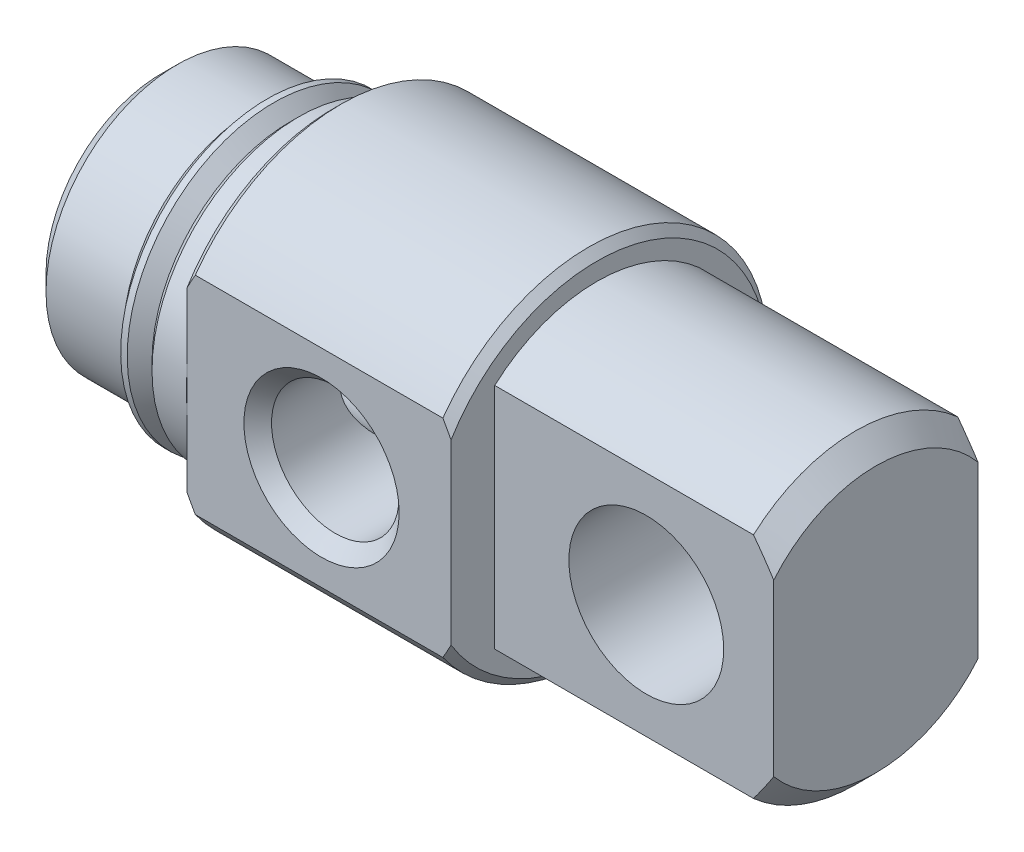
SolidWorks part; units mm, degrees
material "Cast Alloy Steel"
ref_plane "Front Plane" through (0, 0, 0) normal (0, 0, 1) x (1, 0, 0)
ref_plane "Top Plane" through (0, 0, 0) normal (0, 1, 0) x (1, 0, 0)
ref_plane "Right Plane" through (0, 0, 0) normal (1, 0, 0) x (0, 0, -1)
ref_plane "Plane1" through (22.225, 0, 0) normal (1, 0, 0) x (0, 0, -1)
sketch "Sketch1" plane through (0, 0, 0) normal (0, 0, 1) x (1, 0, 0)
  line L0 (0, 0) -> (0, 3.5751)
  line L1 (0, 3.5751) -> (0.508, 4.0831)
  line L2 (0.508, 4.0831) -> (2.9083, 4.0831)
  line L3 (2.9083, 4.0831) -> (3.4671, 3.5242)
  line L4 (3.4671, 3.5242) -> (4.0259, 3.5242)
  line L5 (4.0259, 3.5242) -> (4.0259, 4.3053)
  line L6 (4.0259, 4.3053) -> (4.2799, 4.5593)
  line L7 (4.2799, 4.5593) -> (5.3467, 4.5593)
  line L8 (5.3467, 4.5593) -> (5.3467, 5.3086)
  line L9 (5.3467, 5.3086) -> (5.6007, 5.5626)
  line L10 (5.6007, 5.5626) -> (13.2969, 5.5626)
  line L11 (13.2969, 5.5626) -> (13.5509, 5.3086)
  line L12 (13.5509, 5.3086) -> (13.5509, 0)
  line L13 (13.5509, 0) -> (0, 0)
  line L14 (13.5509, 0) -> (0, 0) construction
revolve "Revolve1" add sketch "Sketch1" angle 360 about L14 reverse direction yes
sketch "Sketch2" plane through (0, 0, 0) normal (0, 0, 1) x (1, 0, 0)
  line L0 (13.5509, 0) -> (13.5509, 4.7625)
  line L1 (13.5509, 4.7625) -> (21.5951, 4.7625)
  line L2 (21.5951, 4.7625) -> (22.225, 4.1326)
  line L3 (22.225, 4.1326) -> (22.225, 0)
  line L4 (22.225, 0) -> (13.5509, 0)
  line L5 (22.225, 0) -> (13.5509, 0) construction
revolve "Revolve2" add sketch "Sketch2" angle 360 about L5 reverse direction yes
cosmetic thread "Cosmetic Thread1" parameters "D1"=8.6741, "D2"=8.2652
sketch "Sketch3" plane through (22.225, 0, 0) normal (1, 0, 0) x (0, 0, -1)
  line L0 (-11.1252, -22.2504) -> (11.1252, -22.2504)
  line L1 (11.1252, -22.2504) -> (11.1252, 22.2504)
  line L2 (11.1252, 22.2504) -> (-11.1252, 22.2504)
  line L3 (-11.1252, 22.2504) -> (-11.1252, -22.2504)
  line L4 (-3.175, -11.1252) -> (3.175, -11.1252)
  line L5 (3.175, -11.1252) -> (3.175, 11.1252)
  line L6 (3.175, 11.1252) -> (-3.175, 11.1252)
  line L7 (-3.175, 11.1252) -> (-3.175, -11.1252)
extrude "Cut-Extrude1" cut sketch "Sketch3" against normal blind 8.6741
ref_plane "Plane2" through (13.5509, 0, 0) normal (1, 0, 0) x (0, 0, -1)
sketch "Sketch4" plane through (13.5509, 0, 0) normal (1, 0, 0) x (0, 0, -1)
  line L0 (-10.0965, 5.5626) -> (-10.0965, -5.5626)
  line L1 (-10.0965, -5.5626) -> (-4.5339, -5.5626)
  line L2 (-4.5339, -5.5626) -> (-4.5339, 5.5626)
  line L3 (-4.5339, 5.5626) -> (-10.0965, 5.5626)
extrude "Cut-Extrude2" cut sketch "Sketch4" against normal blind 8.2042
hole_wizard "Hole1" positions "Sketch6" profile "Sketch5" legacy
sketch "Sketch6" plane through (0, 0, 0) normal (-1, 0, 0) x (0, 0, 1)
  point P0 (0, 0)
sketch "Sketch5" plane through (0, 0, 0) normal (0, 1, 0) x (0, 0, 1)
  line L0 (0, 0) -> (0, 14.6962)
  line L1 (0, 14.6962) -> (1.9837, 13.5509)
  line L2 (1.9837, 13.5509) -> (1.9837, 0)
  line L4 (1.9837, 0) -> (0, 0)
  line L6 (0, 14.6962) -> (-1.9837, 13.5509) construction
  line L7 (0, -4.2442) -> (0, 117.3081) construction
  dimension "Diameter" = 3.9675
  dimension "Depth" = 13.5509
  dimension "Drill Angle" = 120
hole_wizard "Hole2" positions "Sketch8" profile "Sketch7" legacy
sketch "Sketch8" plane through (0, 0, 4.5339) normal (0, 0, 1) x (1, 0, 0)
  point P0 (9.525, 0)
sketch "Sketch7" plane through (9.525, 0, 4.5339) normal (1, 0, 0) x (0, -1, 0)
  line L0 (0, 0) -> (0, 4.5339)
  line L1 (0, 4.5339) -> (1.9837, 4.5339)
  line L2 (1.9837, 4.5339) -> (1.9837, 0.4293)
  line L3 (1.9837, 0.4293) -> (2.413, 0)
  line L4 (2.413, 0) -> (0, 0)
  line L5 (0, -6.4453) -> (0, 115.525) construction
  line L6 (-1.9837, 0.4293) -> (-2.413, 0) construction
  dimension "Diameter" = 3.9675
  dimension "Depth" = 4.5339
  dimension "C-Sink Angle" = 90
  dimension "C-Sink Diameter" = 4.826
cosmetic thread "Cosmetic Thread2" parameters "D1"=2.5502, "D2"=4.826
ref_plane "Plane3" through (0, 0, 0) normal (0, 0.9998, 0.0175) x (1, 0, 0)
ref_plane "Plane4" through (9.525, 0, 0) normal (1, 0, 0) x (0, 0, -1)
ref_plane "Plane5" through (3.4671, 0, 0) normal (1, 0, 0) x (0, 0, -1)
sketch "Sketch9" plane through (0, 0, 0) normal (0, 0, 1) x (1, 0, 0)
  line L0 (3.3065, 4.4751) -> (3.9121, 3.8695)
  line L1 (3.9121, 3.6899) -> (3.7465, 3.5242)
  line L2 (3.7465, 3.5242) -> (3.4671, 3.5242)
  line L3 (3.4671, 3.5242) -> (3.4671, 3.2703)
  line L4 (3.4671, 3.2703) -> (4.0259, 3.2703)
  line L5 (4.0259, 3.2703) -> (4.0259, 4.0431)
  line L6 (4.0259, 4.0431) -> (3.5097, 4.5593)
  line L7 (3.5097, 4.5593) -> (3.3065, 4.5593)
  line L8 (3.3065, 4.5593) -> (3.3065, 4.4751)
  line L9 (4.0259, 0) -> (3.4671, 0) construction
  arc A0 (3.9121, 3.8695) -> (3.9121, 3.6899) centre (3.8223, 3.7797) cw
revolve "Revolve3" add sketch "Sketch9" angle 360 about L9 reverse direction yes
ref_plane "Plane6" through (22.352, 0, 0) normal (1, 0, 0) x (0, 0, -1)
sketch "Sketch10" plane through (0, 0, 0) normal (0, 0, 1) x (1, 0, 0)
  circle A0 centre (18.2626, 0) radius 2.4066
extrude "Cut-Extrude3" cut sketch "Sketch10" along normal blind 4.7625 and the other way blind 4.7625
ref_plane "Plane7" through (13.5509, 0, 0) normal (1, 0, 0) x (0, 0, -1)
ref_plane "Plane8" through (22.225, 0, 0) normal (1, 0, 0) x (0, 0, -1)
ref_plane "Plane9" through (18.2626, 0, 0) normal (1, 0, 0) x (0, 0, -1)
ref_plane "Plane10" through (22.225, 0, 0) normal (1, 0, 0) x (0, 0, -1)
ref_plane "Plane11" through (0, 0, 0) normal (0, 0, 1) x (1, 0, 0)
ref_plane "Plane12" through (13.5509, 0, 0) normal (1, 0, 0) x (0, 0, -1)
ref_plane "Plane13" through (0, 0, 0) normal (0, 1, 0) x (1, 0, 0)
ref_plane "Plane14" through (0, 0, 0) normal (0, 1, 0) x (1, 0, 0)
ref_plane "Plane15" through (13.5509, 0, 0) normal (1, 0, 0) x (0, 0, -1)
ref_plane "1 XY" through (13.5509, 0, 0) normal (1, 0, 0) x (0, 0, -1)
ref_plane "1 XZ" through (0, 0, 0) normal (0, -1, 0) x (-1, 0, 0)
ref_plane "1 YZ" through (0, 0, 0) normal (0, 0, -1) x (-1, 0, 0)
ref_axis "1 X" through (13.5509, 0, 80.9) along (0, 0, -1)
ref_axis "1 Y" through (13.5509, -50, 0) along (0, 1, 0)
ref_axis "1 Z" through (80.9, 0, 0) along (-1, 0, 0)
sketch3d "1"
  point P0 (13.5509, 0, 0)
ref_plane "lovra1 XY" through (22.225, 0, 0) normal (1, 0, 0) x (0, 0, -1)
ref_plane "lovra1 XZ" through (0, 0, 0) normal (0, -1, 0) x (-1, 0, 0)
ref_plane "lovra1 YZ" through (0, 0, 0) normal (0, 0, -1) x (-1, 0, 0)
ref_axis "lovra1 X" through (22.225, 0, 80.9) along (0, 0, -1)
ref_axis "lovra1 Y" through (22.225, -50, 0) along (0, 1, 0)
ref_axis "lovra1 Z" through (80.9, 0, 0) along (-1, 0, 0)
sketch3d "lovra1"
  point P0 (22.225, 0, 0)
ref_plane "lovra2 XY" through (22.225, 0, 0) normal (1, 0, 0) x (0, 0, -1)
ref_plane "lovra2 XZ" through (0, 0, 0) normal (0, -1, 0) x (-1, 0, 0)
ref_plane "lovra2 YZ" through (0, 0, 0) normal (0, 0, -1) x (-1, 0, 0)
ref_axis "lovra2 X" through (22.225, 0, 80.9) along (0, 0, -1)
ref_axis "lovra2 Y" through (22.225, -50, 0) along (0, 1, 0)
ref_axis "lovra2 Z" through (80.9, 0, 0) along (-1, 0, 0)
sketch3d "lovra2"
  point P0 (22.225, 0, 0)
ref_plane "lovra21 XY" through (0, 0, 0) normal (1, 0, 0) x (0, 0, -1)
ref_plane "lovra21 XZ" through (0, 0, 0) normal (0, -1, 0) x (-1, 0, 0)
ref_plane "lovra21 YZ" through (0, 0, 5.2705) normal (0, 0, -1) x (-1, 0, 0)
ref_axis "lovra21 X" through (0, 0, 80.9) along (0, 0, -1)
ref_axis "lovra21 Y" through (0, -50, 5.2705) along (0, 1, 0)
ref_axis "lovra21 Z" through (80.9, 0, 5.2705) along (-1, 0, 0)
sketch3d "lovra21"
  point P0 (0, 0, 5.2705)
ref_plane "lovra22 XY" through (0, 0, 0) normal (1, 0, 0) x (0, 0, -1)
ref_plane "lovra22 XZ" through (0, 0, 0) normal (0, -1, 0) x (-1, 0, 0)
ref_plane "lovra22 YZ" through (0, 0, -5.2705) normal (0, 0, -1) x (-1, 0, 0)
ref_axis "lovra22 X" through (0, 0, 80.9) along (0, 0, -1)
ref_axis "lovra22 Y" through (0, -50, -5.2705) along (0, 1, 0)
ref_axis "lovra22 Z" through (80.9, 0, -5.2705) along (-1, 0, 0)
sketch3d "lovra22"
  point P0 (0, 0, -5.2705)
ref_plane "lovra3 XY" through (22.225, 0, 0) normal (1, 0, 0) x (0, 0, -1)
ref_plane "lovra3 XZ" through (0, 0, 0) normal (0, -1, 0) x (-1, 0, 0)
ref_plane "lovra3 YZ" through (0, 0, 0) normal (0, 0, -1) x (-1, 0, 0)
ref_axis "lovra3 X" through (22.225, 0, 80.9) along (0, 0, -1)
ref_axis "lovra3 Y" through (22.225, -50, 0) along (0, 1, 0)
ref_axis "lovra3 Z" through (80.9, 0, 0) along (-1, 0, 0)
sketch3d "lovra3"
  point P0 (22.225, 0, 0)
ref_plane "olen XY" through (18.2626, 0, 0) normal (1, 0, 0) x (0, 0, -1)
ref_plane "olen XZ" through (0, 0, 0) normal (0, -1, 0) x (-1, 0, 0)
ref_plane "olen YZ" through (0, 0, 0) normal (0, 0, -1) x (-1, 0, 0)
ref_axis "olen X" through (18.2626, 0, 80.9) along (0, 0, -1)
ref_axis "olen Y" through (18.2626, -50, 0) along (0, 1, 0)
ref_axis "olen Z" through (80.9, 0, 0) along (-1, 0, 0)
sketch3d "olen"
  point P0 (18.2626, 0, 0)
ref_plane "p1 XY" through (22.225, 0, 0) normal (1, 0, 0) x (0, 0, -1)
ref_plane "p1 XZ" through (0, 0, 0) normal (0, -1, 0) x (-1, 0, 0)
ref_plane "p1 YZ" through (0, 0, 3.175) normal (0, 0, -1) x (-1, 0, 0)
ref_axis "p1 X" through (22.225, 0, 80.9) along (0, 0, -1)
ref_axis "p1 Y" through (22.225, -50, 3.175) along (0, 1, 0)
ref_axis "p1 Z" through (80.9, 0, 3.175) along (-1, 0, 0)
sketch3d "p1"
  point P0 (22.225, 0, 3.175)
ref_plane "p2 XY" through (22.225, 0, 0) normal (1, 0, 0) x (0, 0, -1)
ref_plane "p2 XZ" through (0, 0, 0) normal (0, -1, 0) x (-1, 0, 0)
ref_plane "p2 YZ" through (0, 0, -3.175) normal (0, 0, -1) x (-1, 0, 0)
ref_axis "p2 X" through (22.225, 0, 80.9) along (0, 0, -1)
ref_axis "p2 Y" through (22.225, -50, -3.175) along (0, 1, 0)
ref_axis "p2 Z" through (80.9, 0, -3.175) along (-1, 0, 0)
sketch3d "p2"
  point P0 (22.225, 0, -3.175)
ref_plane "port XY" through (0, 0, 0) normal (0, 0, 1) x (1, 0, 0)
ref_plane "port XZ" through (0, 0, 0) normal (0, -1, 0) x (-1, 0, 0)
ref_plane "port YZ" through (9.525, 0, 0) normal (1, 0, 0) x (0, 0, -1)
ref_axis "port X" through (-80.9, 0, 0) along (1, 0, 0)
ref_axis "port Y" through (9.525, -50, 0) along (0, 1, 0)
ref_axis "port Z" through (9.525, 0, 80.9) along (0, 0, -1)
sketch3d "port"
  point P0 (9.525, 0, 0)
ref_plane "port2 XY" through (22.225, 0, 0) normal (1, 0, 0) x (0, 0, -1)
ref_plane "port2 XZ" through (0, 0, 0) normal (0, -1, 0) x (-1, 0, 0)
ref_plane "port2 YZ" through (0, 0, 0) normal (0, 0, -1) x (-1, 0, 0)
ref_axis "port2 X" through (22.225, 0, 80.9) along (0, 0, -1)
ref_axis "port2 Y" through (22.225, -50, 0) along (0, 1, 0)
ref_axis "port2 Z" through (80.9, 0, 0) along (-1, 0, 0)
sketch3d "port2"
  point P0 (22.225, 0, 0)
ref_plane "thd1 XY" through (22.225, 0, 0) normal (1, 0, 0) x (0, 0, -1)
ref_plane "thd1 XZ" through (0, 0, 0) normal (0, -1, 0) x (-1, 0, 0)
ref_plane "thd1 YZ" through (0, 0, 4.7625) normal (0, 0, -1) x (-1, 0, 0)
ref_axis "thd1 X" through (22.225, 0, 80.9) along (0, 0, -1)
ref_axis "thd1 Y" through (22.225, -50, 4.7625) along (0, 1, 0)
ref_axis "thd1 Z" through (80.9, 0, 4.7625) along (-1, 0, 0)
sketch3d "thd1"
  point P0 (22.225, 0, 4.7625)
ref_plane "thd2 XY" through (22.225, 0, 0) normal (1, 0, 0) x (0, 0, -1)
ref_plane "thd2 XZ" through (0, 0, 0) normal (0, -1, 0) x (-1, 0, 0)
ref_plane "thd2 YZ" through (0, 0, -4.7625) normal (0, 0, -1) x (-1, 0, 0)
ref_axis "thd2 X" through (22.225, 0, 80.9) along (0, 0, -1)
ref_axis "thd2 Y" through (22.225, -50, -4.7625) along (0, 1, 0)
ref_axis "thd2 Z" through (80.9, 0, -4.7625) along (-1, 0, 0)
sketch3d "thd2"
  point P0 (22.225, 0, -4.7625)
ref_plane "to_mounting_bracket XY" through (13.5509, 0, 0) normal (1, 0, 0) x (0, 0, -1)
ref_plane "to_mounting_bracket XZ" through (0, 0, 0) normal (0, -1, 0) x (-1, 0, 0)
ref_plane "to_mounting_bracket YZ" through (0, 0, 0) normal (0, 0, -1) x (-1, 0, 0)
ref_axis "to_mounting_bracket X" through (13.5509, 0, 80.9) along (0, 0, -1)
ref_axis "to_mounting_bracket Y" through (13.5509, -50, 0) along (0, 1, 0)
ref_axis "to_mounting_bracket Z" through (80.9, 0, 0) along (-1, 0, 0)
sketch3d "to_mounting_bracket"
  point P0 (13.5509, 0, 0)
ref_plane "to_nut XY" through (13.5509, 0, 0) normal (1, 0, 0) x (0, 0, -1)
ref_plane "to_nut XZ" through (0, 0, 0) normal (0, -1, 0) x (-1, 0, 0)
ref_plane "to_nut YZ" through (0, 0, 0) normal (0, 0, -1) x (-1, 0, 0)
ref_axis "to_nut X" through (13.5509, 0, 80.9) along (0, 0, -1)
ref_axis "to_nut Y" through (13.5509, -50, 0) along (0, 1, 0)
ref_axis "to_nut Z" through (80.9, 0, 0) along (-1, 0, 0)
sketch3d "to_nut"
  point P0 (13.5509, 0, 0)
ref_plane "to_pin XY" through (0, 0, 0) normal (0, 0, 1) x (1, 0, 0)
ref_plane "to_pin XZ" through (0, 0, 0) normal (0, -1, 0) x (-1, 0, 0)
ref_plane "to_pin YZ" through (18.2626, 0, 0) normal (1, 0, 0) x (0, 0, -1)
ref_axis "to_pin X" through (-80.9, 0, 0) along (1, 0, 0)
ref_axis "to_pin Y" through (18.2626, -50, 0) along (0, 1, 0)
ref_axis "to_pin Z" through (18.2626, 0, 80.9) along (0, 0, -1)
sketch3d "to_pin"
  point P0 (18.2626, 0, 0)
ref_plane "to_screw XY" through (0, 0, 0) normal (0, 1, 0) x (1, 0, 0)
ref_plane "to_screw XZ" through (0, 0, 0) normal (0, 0, 1) x (1, 0, 0)
ref_plane "to_screw YZ" through (9.525, 0, 0) normal (1, 0, 0) x (0, 0, -1)
ref_axis "to_screw X" through (-80.9, 0, 0) along (1, 0, 0)
ref_axis "to_screw Y" through (9.525, 0, 50) along (0, 0, -1)
ref_axis "to_screw Z" through (9.525, 50, 0) along (0, -1, 0)
sketch3d "to_screw"
  point P0 (9.525, 0, 0)
ref_plane "to_tube XY" through (3.4671, 0, 0) normal (1, 0, 0) x (0, 0, -1)
ref_plane "to_tube XZ" through (0, 0, 0) normal (0, -1, 0) x (-1, 0, 0)
ref_plane "to_tube YZ" through (0, 0, 0) normal (0, 0, -1) x (-1, 0, 0)
ref_axis "to_tube X" through (3.4671, 0, 80.9) along (0, 0, -1)
ref_axis "to_tube Y" through (3.4671, -50, 0) along (0, 1, 0)
ref_axis "to_tube Z" through (80.9, 0, 0) along (-1, 0, 0)
sketch3d "to_tube"
  point P0 (3.4671, 0, 0)
